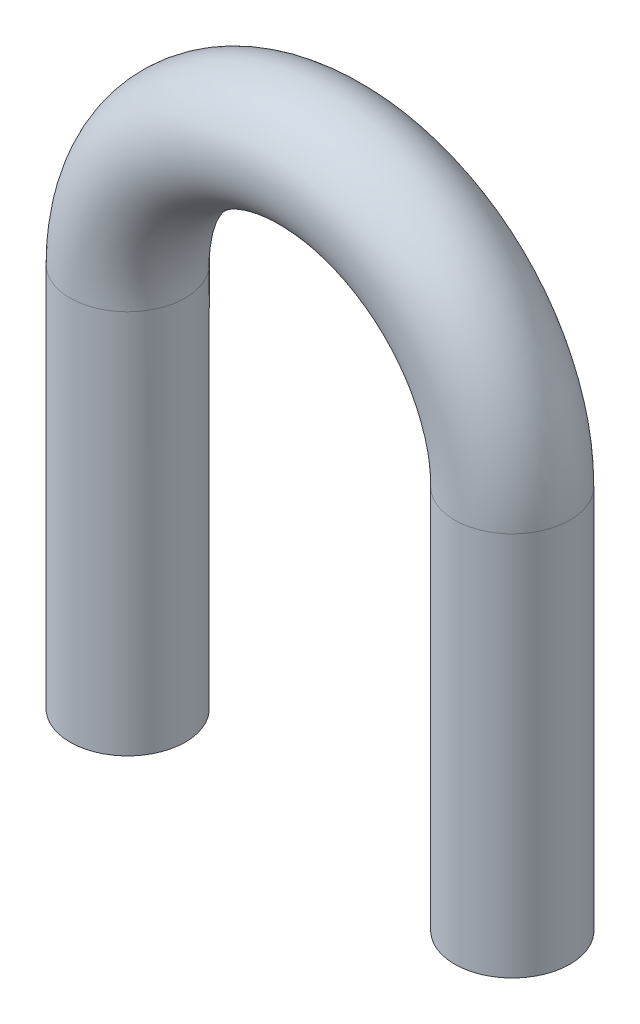
SolidWorks part; units mm, degrees
material "AISI Type A2 Tool Steel"
ref_plane "Front Plane" through (0, 0, 0) normal (0, 0, 1) x (1, 0, 0)
ref_plane "Top Plane" through (0, 0, 0) normal (0, 1, 0) x (1, 0, 0)
ref_plane "Right Plane" through (0, 0, 0) normal (1, 0, 0) x (0, 0, -1)
sketch "Sketch1" plane through (0, 0, 0) normal (0, 1, 0) x (1, 0, 0)
  line L0 (0, -188.2675) -> (0, 9225.1073) construction
  circle A0 centre (5, 0) radius 1.5
  point P3 (5, 1.8458)
  dimension "D2" = 3
  dimension "D1" = 10
revolve "Revolve1" add sketch "Sketch1" angle 180 about L0 reverse direction yes
sketch "Sketch2" plane through (0, 0, 0) normal (0, -1, 0) x (1, 0, 0)
  circle A0 centre (5, 0) radius 1.5 construction
  circle A1 centre (-5, 0) radius 1.5 construction
  circle A2 centre (5, 0) radius 1.5
  circle A3 centre (-5, 0) radius 1.5
extrude "Boss-Extrude1" add sketch "Sketch2" along normal blind 10
